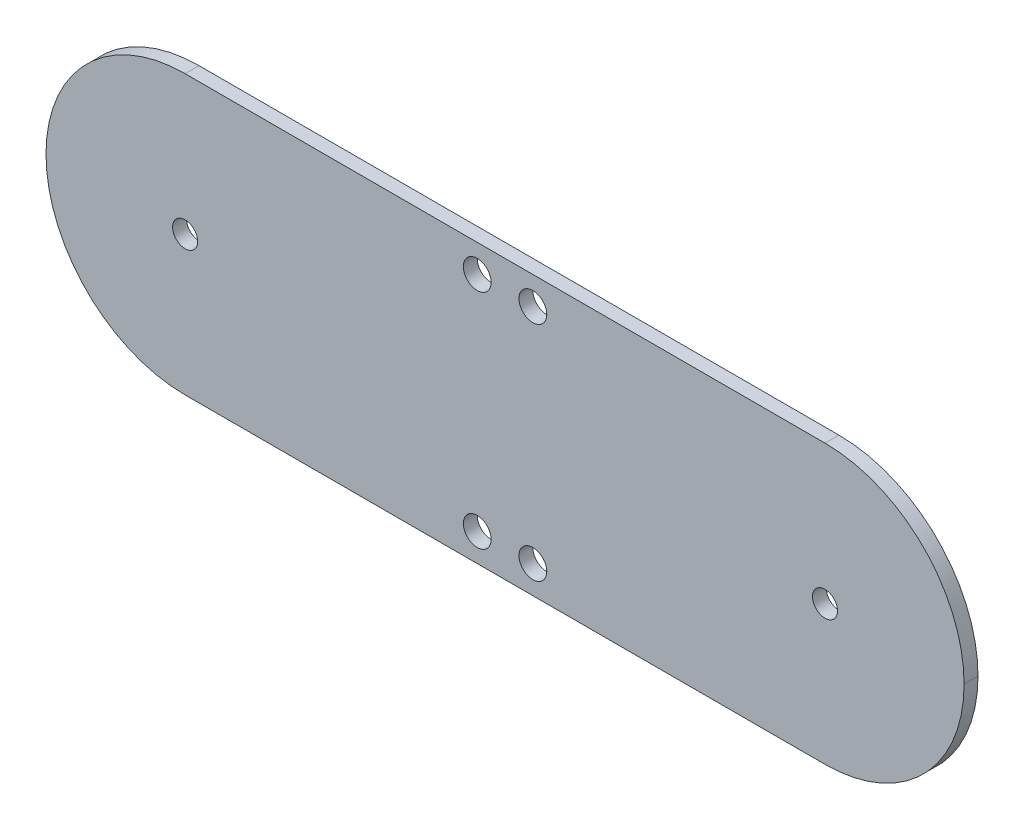
SolidWorks part; units mm, degrees
ref_plane "Front Plane" through (0, 0, 0) normal (0, 0, 1) x (1, 0, 0)
ref_plane "Top Plane" through (0, 0, 0) normal (0, 1, 0) x (1, 0, 0)
ref_plane "Right Plane" through (0, 0, 0) normal (1, 0, 0) x (0, 0, -1)
sketch "Sketch1" plane through (0, 0, 0) normal (0, 0, 1) x (1, 0, 0)
  line L1 (82.5, 25) -> (-82.5, 25)
  line L2 (82.5, 25) -> (82.5, -25)
  line L3 (82.5, -25) -> (-82.5, -25)
  line L4 (-82.5, 25) -> (-82.5, -25)
  line L5 (82.5, 25) -> (-82.5, -25) construction
  line L6 (82.5, -25) -> (-82.5, 25) construction
  point P0 (0, 0)
  dimension "D1" = 50
  dimension "D2" = 165
extrude "Boss-Extrude1" add sketch "Sketch1" along normal blind 2.5
fillet "Fillet1" radius 25 4 edges at (-82.5, -25, 1.25) (-82.5, 25, 1.25) (82.5, -25, 1.25) (82.5, 25, 1.25)
sketch "Sketch2" plane through (0, 0, 2.5) normal (0, 0, 1) x (1, 0, 0)
  line L0 (0, 0) -> (0, 20)
  line L1 (0, 20) -> (-5, 20)
  line L2 (-5, 20) -> (5, 20)
  circle A0 centre (-5, 20) radius 2.5
  circle A1 centre (5, 20) radius 2.5
  dimension "D4" = 5
  dimension "D5" = 5
  dimension "D1" = 20
  dimension "D2" = 5
  dimension "D3" = 10
extrude "Cut-Extrude1" cut sketch "Sketch2" against normal blind 2.5 contours A0 | A1 region at (-7.4293, 20, 2.5) region at (5, 22.4293, 2.5)
mirror "Mirror1" about plane through (0, 0, 0) normal (0, 1, 0) of "Cut-Extrude1"
sketch "Sketch4" plane through (0, 0, 2.5) normal (0, 0, 1) x (1, 0, 0)
  line L0 (0, 0) -> (-57.5, 0)
  circle A0 centre (-57.5, 0) radius 2.25
  dimension "D2" = 4.5
  dimension "D1" = 57.5
extrude "Cut-Extrude2" cut sketch "Sketch4" against normal blind 10 contours A0 region at (-59.6864, 0, 2.5)
mirror "Mirror2" about plane through (0, 0, 0) normal (1, 0, 0) of "Cut-Extrude2"
